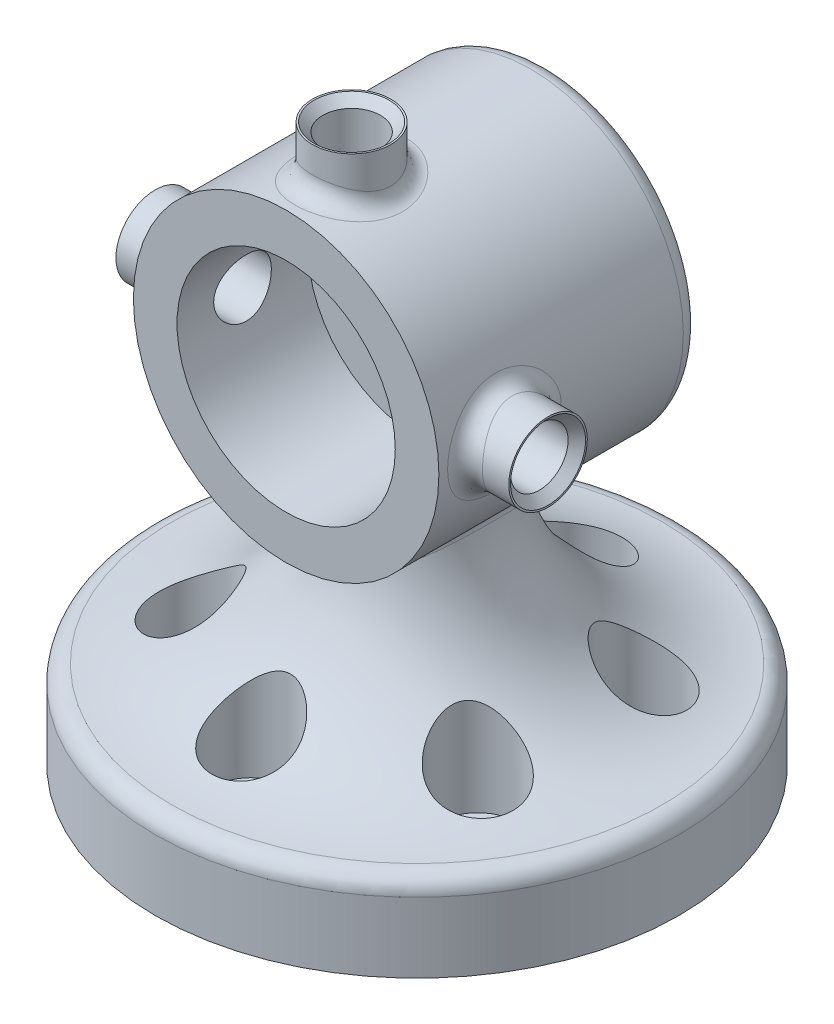
SolidWorks part; units mm, degrees
ref_plane "Front Plane" through (0, 0, 0) normal (0, 0, 1) x (1, 0, 0)
ref_plane "Top Plane" through (0, 0, 0) normal (0, 1, 0) x (1, 0, 0)
ref_plane "Right Plane" through (0, 0, 0) normal (1, 0, 0) x (0, 0, -1)
sketch "Sketch1" plane through (0, 0, 0) normal (0, 1, 0) x (1, 0, 0)
  circle A0 centre (0, 0) radius 30
  dimension "D1" = 60
extrude "Boss-Extrude1" add sketch "Sketch1" along normal blind 10
sketch "Sketch2" plane through (0, 10, 0) normal (0, 1, 0) x (1, 0, 0)
  circle A0 centre (0, 0) radius 19 construction
  circle A1 centre (0, 19) radius 4.5
  circle A2 centre (16.4545, 9.5) radius 4.5
  circle A3 centre (16.4545, -9.5) radius 4.5
  circle A4 centre (0, -19) radius 4.5
  circle A5 centre (-16.4545, -9.5) radius 4.5
  circle A6 centre (-16.4545, 9.5) radius 4.5
  point P18 (0, 0)
  dimension "D1" = 38
  dimension "D2" = 9
  dimension "D3" = 6
extrude "Cut-Extrude1" cut sketch "Sketch2" against normal blind 5
sketch "Sketch3" plane through (0, 5, 0) normal (0, 1, 0) x (1, 0, 0)
  circle A0 centre (0, 19) radius 2.75
  circle A1 centre (16.4545, 9.5) radius 2.75
  circle A2 centre (16.4545, -9.5) radius 2.75
  circle A3 centre (0, -19) radius 2.75
  circle A4 centre (-16.4545, -9.5) radius 2.75
  circle A5 centre (-16.4545, 9.5) radius 2.75
  point P15 (0, 0)
  dimension "D1" = 5.5
  dimension "D2" = 6
extrude "Cut-Extrude2" cut sketch "Sketch3" against normal through all
sketch "Sketch4" plane through (0, 0, 0) normal (0, 0, 1) x (1, 0, 0)
  circle A0 centre (0, 45) radius 12.5
  circle A1 centre (0, 45) radius 17.5
  dimension "D1" = 25
  dimension "D2" = 5
  dimension "D3" = 45
extrude "Boss-Extrude3" add sketch "Sketch4" along normal blind 15
sketch "Sketch5" plane through (0, 0, 0) normal (0, 0, -1) x (-1, 0, 0)
  circle A0 centre (0, 45) radius 17.5
  circle A1 centre (0, 45) radius 17.5 construction
extrude "Boss-Extrude4" add sketch "Sketch5" along normal blind 15
sketch "Sketch10" plane through (0, 0, 0) normal (0, 0, 1) x (1, 0, 0)
  line L0 (0, 0) -> (0, 29.9917) construction
  line L3 (4.5, 10) -> (-4.5, 10) construction
  line L4 (0, 10) -> (0, 29.9917)
  line L5 (0, 29.9917) -> (-9, 29.9917)
  line L8 (-28.9917, 10) -> (0, 10)
  line L9 (30, 10) -> (-30, 10) construction
  arc A4 (-9, 29.9917) -> (-28.9917, 10) centre (-28.9917, 29.9917) cw
  circle A6 centre (0, 45) radius 17.5 construction
  point P4 (-8.0678, 29.4707)
  point P6 (-33.1877, 29.8444)
  point P8 (-29.3848, 10)
  point P11 (-8, 29.0268)
  point P14 (0, 0)
  point P15 (0, 0)
  point P22 (-8.0013, 29.4363)
  dimension "D1" = 9
revolve "Revolve1" add sketch "Sketch10" angle 360 about L0
sketch "Sketch11" plane through (0, 10, 0) normal (0, -1, 0) x (1, 0, 0)
  circle A0 centre (0, 19) radius 4.5
  circle A1 centre (16.4545, 9.5) radius 4.5
  circle A2 centre (16.4545, -9.5) radius 4.5
  circle A3 centre (0, -19) radius 4.5
  circle A4 centre (-16.4545, -9.5) radius 4.5
  circle A5 centre (-16.4545, 9.5) radius 4.5
  point P4 (25.857, 10.8635)
  point P5 (0, 0)
  point P15 (0, 0)
  dimension "D1" = 9
  dimension "D2" = 6
extrude "Cut-Extrude3" cut sketch "Sketch11" against normal up to surface (6.22 mm away)
fillet "Fillet1" radius 2 3 edges at (8.6668, 29.7968, 2.4297) (0, 10, 30) (-17.5, 45, -15)
ref_plane "Plane2" through (-22.5, 0, 0) normal (1, 0, 0) x (0, 0, -1)
sketch "Sketch12" plane through (-22.5, 0, 0) normal (1, 0, 0) x (0, 0, -1)
  line L0 (-15, 62.5) -> (-15, 27.5) construction
  line L1 (-15, 27.5) -> (-11.5697, 27.5) construction
  circle A0 centre (-7.5, 45) radius 4.5
  point P4 (-7.5, 47.8852)
  dimension "D1" = 9
  dimension "D2" = 7.5
  dimension "D3" = 17.5
extrude "Boss-Extrude5" add sketch "Sketch12" along normal up to next
sketch "Sketch13" plane through (-22.5, 0, 0) normal (-1, 0, 0) x (0, 0, 1)
  circle A0 centre (7.5, 45) radius 3.3
  dimension "D1" = 6.6
extrude "Cut-Extrude4" cut sketch "Sketch13" against normal up to next
pattern_circular "CirPattern1" count 3 over 180 about axis through (0, 45, 0) along (0, 0, 1) of "Boss-Extrude5", "Cut-Extrude4"
chamfer "Chamfer1" distance 1 angle 45 3 edges at (22.5, 45, 10.8) (0, 67.5, 10.8) (-22.5, 45, 10.8)
fillet "Fillet3" radius 2 3 edges at (17.4783, 44.1286, 11.9148) (4.4146, 61.934, 6.6272) (-17.4783, 44.1286, 3.0852)
